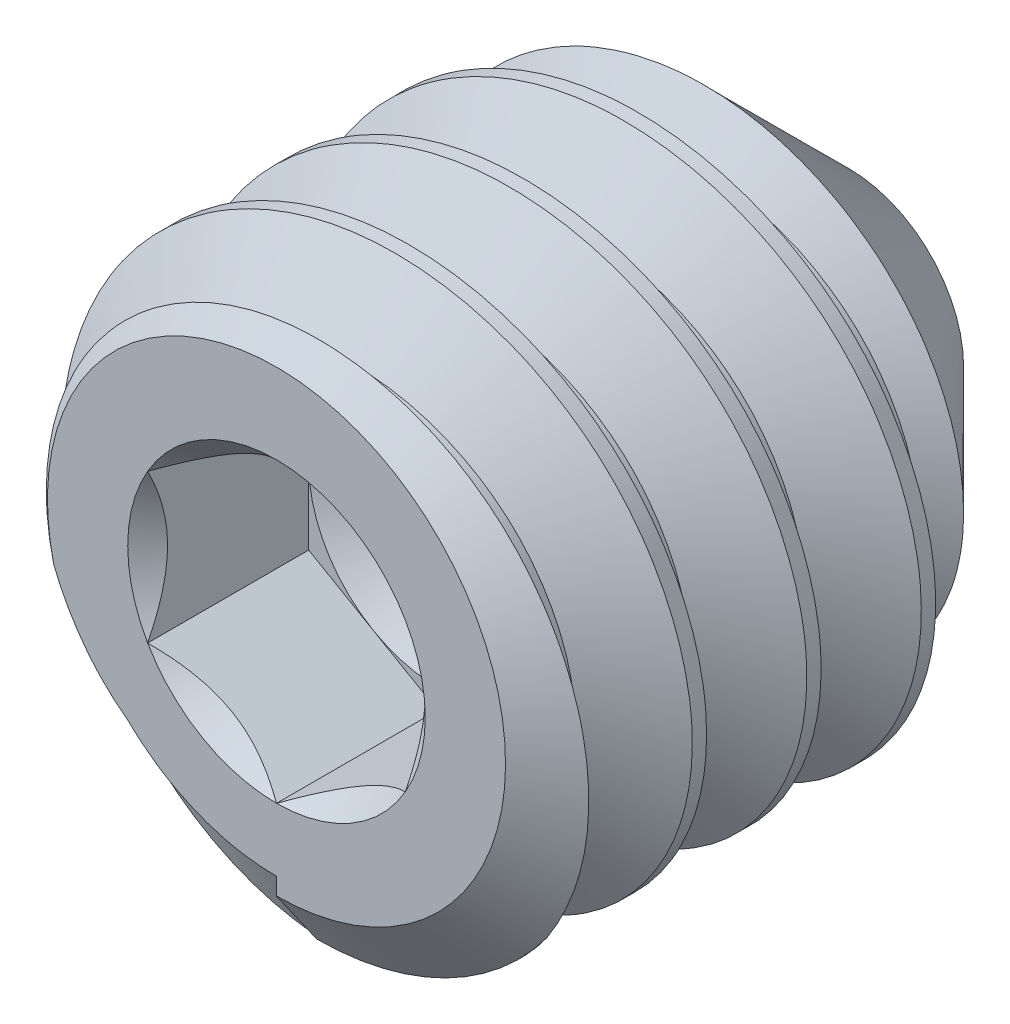
SolidWorks part; units mm, degrees
ref_plane "Front" through (0, 0, 0) normal (0, 0, 1) x (1, 0, 0)
ref_plane "Top" through (0, 0, 0) normal (0, 1, 0) x (1, 0, 0)
ref_plane "Right" through (0, 0, 0) normal (1, 0, 0) x (0, 0, -1)
sketch "Sketch1" plane through (0, 0, 0) normal (1, 0, 0) x (0, 0, -1)
  line L0 (-0.8798, 0) -> (-0.8798, 0.8)
  line L1 (-0.8798, 0.8) -> (-0.7398, 1)
  line L2 (-0.7398, 1) -> (0.5202, 1)
  line L3 (0.5202, 1) -> (1.1202, 0.4)
  line L4 (1.1202, 0.4) -> (0.8798, 0)
  line L5 (0.8798, 0) -> (-0.8798, 0)
  line L6 (0.8798, 0) -> (1.1202, 0) construction
  line L7 (1.1202, 0) -> (1.1202, 0.4) construction
  line L8 (1.1202, -0.4) -> (0.8798, 0) construction
  line L9 (-0.7398, -1) -> (0.5202, -1) construction
  line L10 (-0.8798, 0.8) -> (-1.2798, 0.8) construction
  point P11 (-0.2798, -1)
  point P12 (-0.8798, 1)
  point P13 (1.1202, 1)
  dimension "Dia" = 2
  dimension "Length" = 2
  dimension "D3" = 35
  dimension "D5" = 118
  dimension "D6" = 45
  dimension "Pitch" = 0.4
  dimension "D1" = 0.2
  dimension "D2" = 1.4
  dimension "D4" = 0.6
revolve "Revolve1" add sketch "Sketch1" angle 360 about L6
sketch "Sketch2" plane through (0, 0, 0.8798) normal (0, 0, 1) x (1, 0, 0)
  line L1 (0, 0.5196) -> (-0.45, 0.2598)
  line L2 (-0.45, 0.2598) -> (-0.45, -0.2598)
  line L3 (-0.45, -0.2598) -> (0, -0.5196)
  line L4 (0, -0.5196) -> (0.45, -0.2598)
  line L5 (0.45, -0.2598) -> (0.45, 0.2598)
  line L6 (0.45, 0.2598) -> (0, 0.5196)
  circle A0 centre (0, 0) radius 0.45 construction
  circle A1 centre (0, 0) radius 1 construction
extrude "Cut-Extrude1" cut sketch "Sketch2" against normal blind 0.5625
sketch "Sketch3" plane through (0, 0, 0.8798) normal (0, 0, 1) x (1, 0, 0)
  circle A0 centre (0, 0) radius 0.5196
extrude "Cut-Extrude2" cut sketch "Sketch3" against normal through all draft 45
sketch "Sketch4" plane through (0, 0, 0.3173) normal (0, 0, 1) x (1, 0, 0)
  circle A0 centre (0, 0) radius 0.45 construction
  circle A1 centre (0, 0) radius 0.45
extrude "Cut-Extrude3" cut sketch "Sketch4" against normal through all draft 60
ref_plane "Plane1" through (0, 0, -1.1202) normal (0, 0, 1) x (1, 0, 0)
sketch "Sketch5" plane through (0, 0, -1.1202) normal (0, 0, 1) x (1, 0, 0)
  circle A0 centre (0, 0) radius 1 construction
  circle A1 centre (0, 0) radius 1
curve "Helix/Spiral1" pitch 0.4 height 2.2 radius 1 centre (0, 0, -1.1202) axis (0, 0, 1) start towards (0, 1, 0)
sketch "Sketch6" plane through (0, 0, 0) normal (1, 0, 0) x (0, 0, -1)
  line L0 (1.0952, 1.0433) -> (1.4952, 1.0433) construction
  line L1 (1.4952, 1.0433) -> (1.2952, 0.6969) construction
  line L2 (1.2952, 0.6969) -> (1.0952, 1.0433) construction
  line L3 (1.2952, 1.0433) -> (1.2952, 1) construction
  line L4 (1.1202, 1) -> (1.4702, 1) construction
  line L5 (1.2952, 0.7402) -> (1.2952, 0.6969) construction
  line L6 (1.2702, 0.7402) -> (1.1077, 1.0217)
  line L7 (1.1077, 1.0217) -> (1.4827, 1.0217)
  line L8 (1.1077, 1.0217) -> (1.4827, 1.0217) construction
  line L10 (1.2702, 0.7402) -> (1.3202, 0.7402) construction
  line L12 (1.3202, 0.7402) -> (1.2702, 0.7402)
  line L13 (1.4827, 1.0217) -> (1.3202, 0.7402)
  point P9 (1.2952, 1)
  point P14 (1.2952, 1.0217)
  point P15 (1.2952, 1.0217)
  point P16 (1.2952, 0.7402)
  dimension "D1" = 0.4
  dimension "D2" = 0.05
sweep "Cut-Sweep1" cut profiles "Sketch6" path "Helix/Spiral1"
ref_axis "Center Axis 1" through (0, 0, -1.1202) along (0, 0, 1)
ref_plane "Contact Plane 1" through (0, 0, 0.8798) normal (0, 0, 1) x (1, 0, 0)
ref_plane "Contact Plane 2" through (0, 0, -1.1202) normal (0, 0, 1) x (1, 0, 0)
equation "\"D3@Helix/Spiral1\" = \"Length@Sketch1\" * 1.1"
equation "\"hex Depth@Cut-Extrude1\" = \"Hex@Sketch2\" * .625"
equation "\"D1@Sketch6\" = \"Pitch@Sketch1\""
equation "\"D2@Sketch6\" = \"D1@Sketch6\" / 8"
equation "\"D1@Sketch1\" = \"Pitch@Sketch1\" * .5"
equation "\"D2@Sketch1\" = \"Pitch@Sketch1\" * 3.5"
equation "\"D1@Helix/Spiral1\" = \"Pitch@Sketch1\""
equation "\"D4@Sketch1\" = \"Pitch@Sketch1\" * 1.5"
